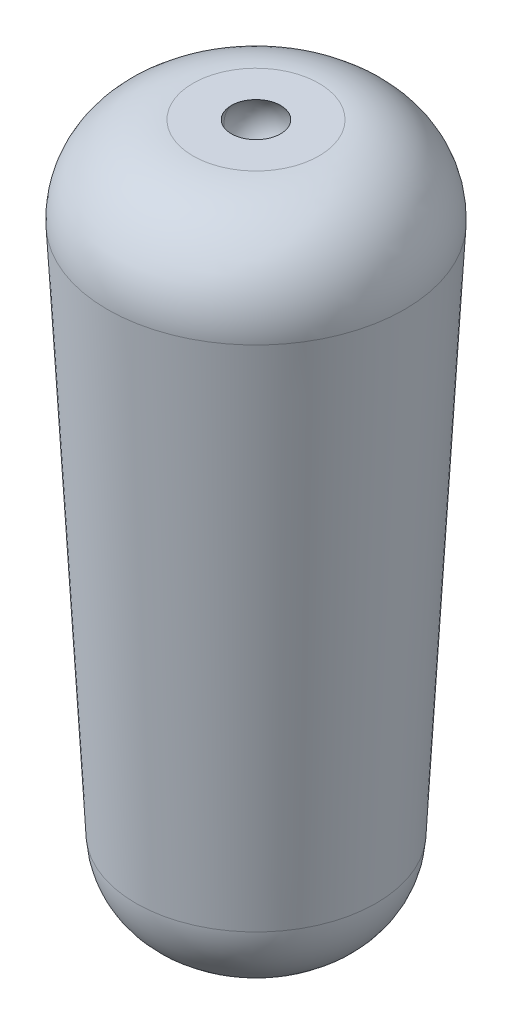
SolidWorks part; units mm, degrees
ref_plane "Front" through (0, 0, 0) normal (0, 0, 1) x (1, 0, 0)
ref_plane "Top" through (0, 0, 0) normal (0, 1, 0) x (1, 0, 0)
ref_plane "Right" through (0, 0, 0) normal (1, 0, 0) x (0, 0, -1)
sketch "Sketch1" plane through (0, 0, 0) normal (0, 1, 0) x (1, 0, 0)
  circle A0 centre (0, 0) radius 90.9577
  dimension "D1" = 181.9155
ref_plane "Plane1" through (0, -415, 0) normal (0, 1, 0) x (-1, 0, 0)
sketch "Sketch2" plane through (0, -415, 0) normal (0, 1, 0) x (-1, 0, 0)
  circle A0 centre (0, 0) radius 68.7236
  dimension "D1" = 137.4472
ref_axis "Axis1" through (0, -415, 0) along (0, 1, 0)
loft "Loft1" add profiles "Sketch1", "Sketch2" connector at (-10.3219, 0, -90.3702) connector at (-10.5801, -415, -67.9043)
sketch "Sketch3" plane through (0, -415, 0) normal (0, -1, 0) x (1, 0, 0)
  circle A0 centre (0, 0) radius 68.7236 construction
  point P0 (0, 0)
fillet "Fillet1" radius 50.8 2 edges at (0, 0, 90.9577) (0, -415, 68.7236)
sketch "Sketch4" plane through (0, 0, 0) normal (0, 1, 0) x (-1, 0, 0)
  point P0 (0, 0)
sketch "Sketch5" plane through (0, 0, 0) normal (0, 0, 1) x (1, 0, 0)
  line L0 (0, -415) -> (0, 0) construction
  circle A0 centre (0, -12.2416) radius 19.05
  dimension "D1" = 38.1
extrude "Boss-Extrude1" add sketch "Sketch5" along normal mid plane 38.1 separate body contours A0
fillet "Fillet2" radius 19.05 2 edges at (19.05, -12.2416, -19.05) (19.05, -12.2416, 19.05)
combine bodies "Combine1" operation type subtract main body 101 bodies to subtract 102
sketch "Sketch6" plane through (0, -415, 0) normal (0, -1, 0) x (1, 0, 0)
  circle A0 centre (0, 0) radius 19.05
  dimension "D3" = 38.1
extrude "Cut-Extrude1" cut sketch "Sketch6" against normal blind 2.54
